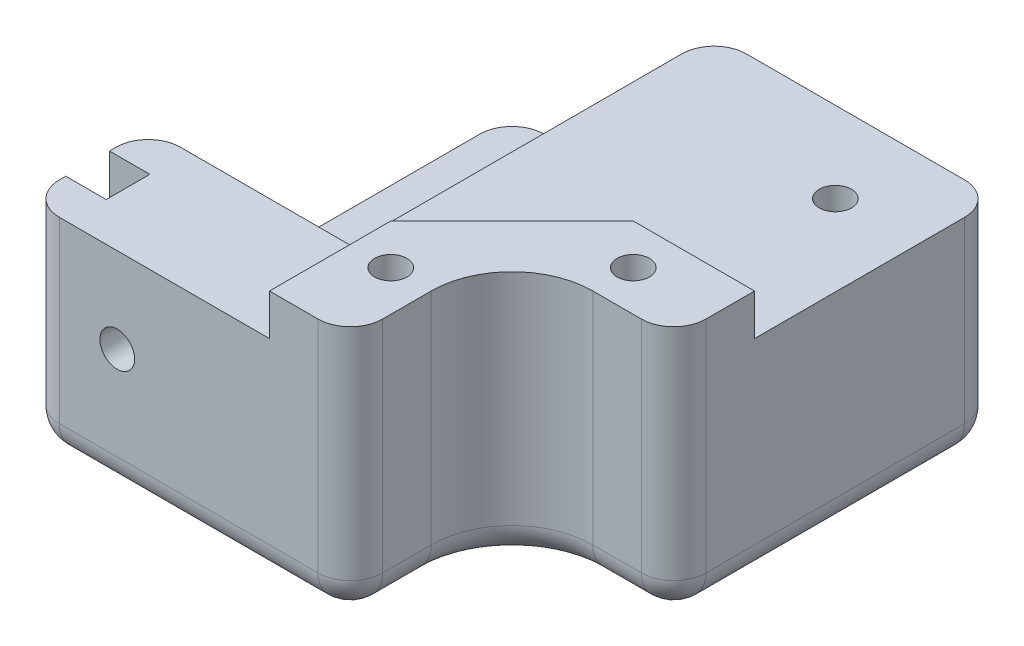
SolidWorks part; units mm, degrees
ref_plane "Front Plane" through (0, 0, 0) normal (0, 0, 1) x (1, 0, 0)
ref_plane "Top Plane" through (0, 0, 0) normal (0, 1, 0) x (1, 0, 0)
ref_plane "Right Plane" through (0, 0, 0) normal (1, 0, 0) x (0, 0, -1)
sketch "Sketch1" plane through (0, 0, 0) normal (0, 1, 0) x (1, 0, 0)
  line L0 (40, 0) -> (40, 20)
  line L1 (0, 0) -> (40, 0)
  line L2 (0, 0) -> (0, 60)
  line L3 (0, 60) -> (60, 60)
  line L4 (60, 20) -> (60, 60)
  line L5 (40, 20) -> (60, 20)
  line L6 (40, 10) -> (0, 10) construction
  line L7 (20, 10) -> (20, 0) construction
  line L8 (40, 20) -> (0, 60) construction
  line L9 (50, 20) -> (50, 60) construction
  line L10 (11.1668, 28) -> (11.1668, 48) construction
  line L17 (6.6668, 28) -> (6.6668, 48)
  line L18 (15.6668, 28) -> (15.6668, 48)
  circle A0 centre (35, 10) radius 2
  circle A2 centre (50, 25) radius 2
  circle A3 centre (50, 50) radius 2
  arc A4 (15.6668, 48) -> (6.6668, 48) centre (11.1668, 48) ccw
  arc A5 (6.6668, 28) -> (15.6668, 28) centre (11.1668, 28) ccw
  dimension "D4" = 4
  dimension "D5" = 10
  dimension "D7" = 9
  dimension "D1" = 40
  dimension "D2" = 60
  dimension "D3" = 5
  dimension "D6" = 11.1668
  dimension "D8" = 12
  dimension "D9" = 20
extrude "Boss-Extrude1" add sketch "Sketch1" along normal blind 26.1
sketch "Sketch2" plane through (0, 0, -60) normal (0, 0, -1) x (-1, 0, 0)
  line L0 (0, 26.1) -> (0, 0) construction
  line L1 (0, 5) -> (-25, 5)
  line L2 (0, 5) -> (0, 26.1)
  line L3 (0, 26.1) -> (-25, 26.1)
  line L4 (-25, 5) -> (-25, 26.1)
  line L6 (-60, 26.1) -> (0, 26.1) construction
  line L7 (-60, 0) -> (0, 0) construction
  dimension "D1" = 5
  dimension "D2" = 25
extrude "Cut-Extrude1" cut sketch "Sketch2" against normal blind 45
sketch "Sketch3" plane through (0, 26.1, 0) normal (0, 1, 0) x (1, 0, 0)
  line L0 (60, 30) -> (45, 30)
  line L1 (60, 20) -> (60, 60) construction
  line L2 (45, 30) -> (30, 15)
  line L3 (30, 15) -> (30, 0)
  line L4 (0, 0) -> (40, 0) construction
  line L5 (40, 0) -> (40, 20) construction
  line L6 (40, 20) -> (60, 20) construction
  line L7 (60, 30) -> (60, 20)
  line L8 (60, 20) -> (40, 20)
  line L9 (40, 20) -> (40, 0)
  line L10 (40, 0) -> (30, 0)
  dimension "D1" = 10
  dimension "D2" = 15
extrude "Boss-Extrude2" add sketch "Sketch3" along normal blind 5.1
fillet "Fillet1" radius 10 1 edges at (40, 15.6, -20)
sketch "Sketch4" plane through (0, 0, 0) normal (0, -1, 0) x (1, 0, 0)
  circle A0 centre (35, -10) radius 3.65
  circle A1 centre (50, -25) radius 3.65
  circle A2 centre (50, -50) radius 3.65
  dimension "D1" = 7.3
extrude "Cut-Extrude2" cut sketch "Sketch4" against normal blind 20
sketch "Sketch5" plane through (0, 0, 0) normal (0, 0, 1) x (1, 0, 0)
  line L0 (11.1668, 26.1) -> (11.1668, 5) construction
  line L1 (0, 26.1) -> (30, 26.1) construction
  line L2 (11.1668, 5) -> (0, 5) construction
  line L3 (0, 26.1) -> (0, 0) construction
  circle A0 centre (11.1668, 15.55) radius 2.15
  dimension "D3" = 4.3
  dimension "D1" = 21.1
  dimension "D2" = 11.1668
extrude "Cut-Extrude3" cut sketch "Sketch5" against normal blind 20
fillet "Fillet2" radius 4 14 edges at (40, 0, -5) (55, 0, -20) (60, 0, -40) (30, 0, -60) (0, 0, -30) (0, 15.55, -15) (25, 15.55, -60) (60, 13.05, -60) (0, 13.05, 0) (60, 15.6, -20) (40, 15.6, 0) (20, 0, 0) (42.9289, 0, -17.0711) (0, 2.5, -60)
chamfer "Chamfer1" distance 4.5 angle 45 4 edges at (26.1716, 5, -58.8284) (1.1716, 5, -13.8284) (25, 5, -35.5) (14.5, 5, -15)
sketch "Sketch6" plane through (0, 0, 0) normal (-1, 0, 0) x (0, 0, 1)
  line L0 (-4, 4) -> (-4, 26.1) construction
  line L1 (-4, 15.05) -> (-11, 15.05)
  line L2 (-4, 15.05) -> (-4, 18.25)
  line L3 (-4, 18.25) -> (-4.8, 18.25)
  line L4 (-11, 15.05) -> (-11, 18.25)
  line L5 (-11, 26.1) -> (-11, 9.5) construction
  line L6 (-11, 26.1) -> (-4, 26.1) construction
  line L8 (-4.8, 18.25) -> (-4.8, 26.1)
  line L9 (-4.8, 26.1) -> (-10.2, 26.1)
  line L10 (-10.2, 18.25) -> (-10.2, 26.1)
  line L11 (-7.5, 15.05) -> (-7.5, 26.1) construction
  line L12 (-10.2, 18.25) -> (-11, 18.25)
  point P16 (-7.5, 26.1)
  dimension "D1" = 3.2
  dimension "D2" = 2.7
extrude "Cut-Extrude4" cut sketch "Sketch6" against normal blind 5
sketch "Sketch7" plane through (0, 26.1, 0) normal (0, -1, 0) x (1, 0, 0)
  circle A0 centre (35, -10) radius 2 construction
  circle A1 centre (50, -25) radius 2 construction
  circle A2 centre (35, -10) radius 2
  circle A3 centre (50, -25) radius 2
extrude "Cut-Extrude5" cut sketch "Sketch7" against normal blind 10
